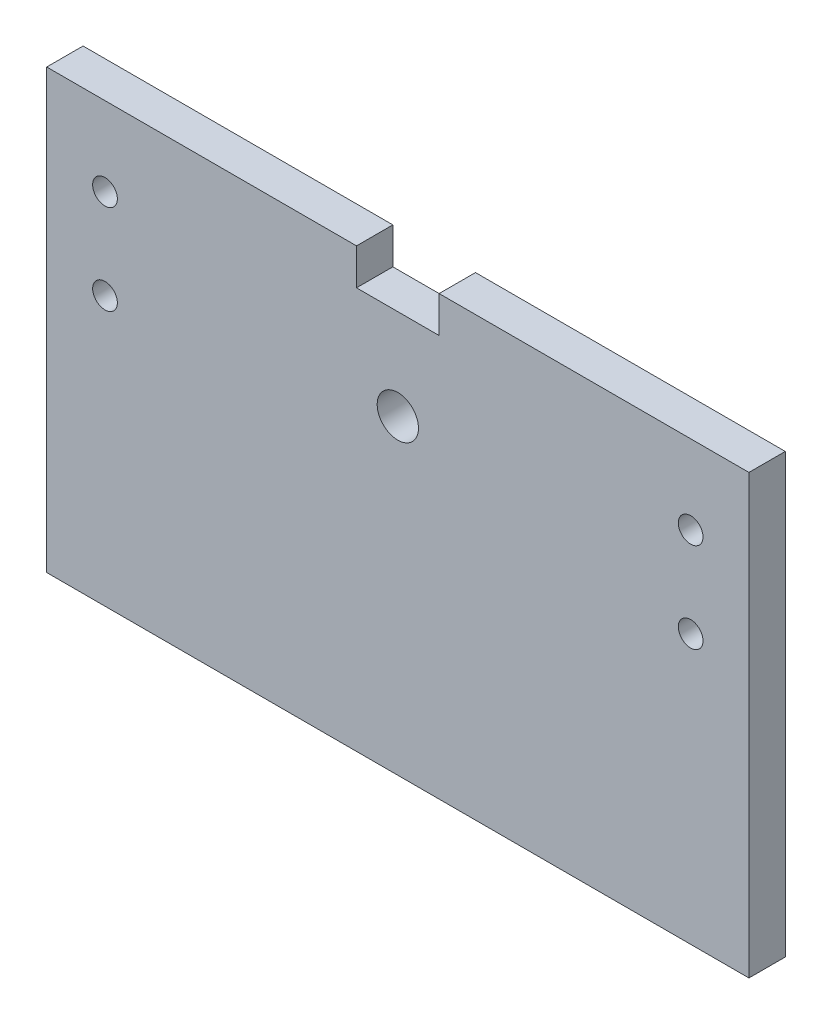
SolidWorks part; units mm, degrees
ref_plane "Front Plane" through (0, 0, 0) normal (0, 0, 1) x (1, 0, 0)
ref_plane "Top Plane" through (0, 0, 0) normal (0, 1, 0) x (1, 0, 0)
ref_plane "Right Plane" through (0, 0, 0) normal (1, 0, 0) x (0, 0, -1)
sketch "Sketch1" plane through (0, 0, 0) normal (0, 0, 1) x (1, 0, 0)
  line L0 (-6.35, 33.655) -> (-6.35, 28.067)
  line L1 (-53.975, -33.655) -> (53.975, -33.655)
  line L2 (-53.975, -33.655) -> (-53.975, 33.655)
  line L3 (-53.975, 33.655) -> (-6.35, 33.655)
  line L4 (53.975, -33.655) -> (53.975, 33.655)
  line L5 (-53.975, -33.655) -> (53.975, 33.655) construction
  line L6 (-53.975, 33.655) -> (53.975, -33.655) construction
  line L7 (-6.35, 28.067) -> (6.35, 28.067)
  line L8 (6.35, 28.067) -> (6.35, 33.655)
  line L9 (6.35, 33.655) -> (53.975, 33.655)
  point P0 (0, 0)
  dimension "D1" = 107.95
  dimension "D2" = 67.31
  dimension "D3" = 5.588
  dimension "D4" = 12.7
extrude "Boss-Extrude1" add sketch "Sketch1" along normal mid plane 5.588
sketch "Sketch2" plane through (0, 0, -2.794) normal (0, 0, -1) x (-1, 0, 0)
  point P0 (-45.0148, 21.5198)
  point P1 (-45.0148, 7.6902)
  point P3 (45.0148, 21.5198)
  point P5 (45.0148, 7.6902)
hole_wizard "#6 Clearance Hole1" positions "Sketch3" profile "Sketch4" hole size "#6" standard "ANSI Inch" end condition through all
sketch "Sketch3" plane through (0, 0, -2.794) normal (0, 0, -1) x (-1, 0, 0)
  point P0 (-45.0148, 21.5198)
  point P3 (-45.0148, 7.6902)
  point P6 (45.0148, 21.5198)
  point P9 (45.0148, 7.6902)
sketch "Sketch4" plane through (45.0148, 21.5198, -2.794) normal (1, 0, 0) x (0, 1, 0)
  line L0 (0, 0) -> (0, 5.588)
  line L1 (0, 5.588) -> (1.8986, 5.588)
  line L2 (1.8986, 5.588) -> (1.8986, 0)
  line L5 (1.8986, 0) -> (0, 0)
  line L11 (0, -6.35) -> (0, 107.95) construction
  dimension "Thru Hole Dia." = 3.7973
  dimension "Thru Hole Depth" = 5.588
sketch "Sketch5" plane through (0, 0, -2.794) normal (0, 0, -1) x (-1, 0, 0)
  circle A0 centre (0, 14.1345) radius 3.175
  dimension "D1" = 6.35
extrude "Cut-Extrude1" cut sketch "Sketch5" against normal up to next
